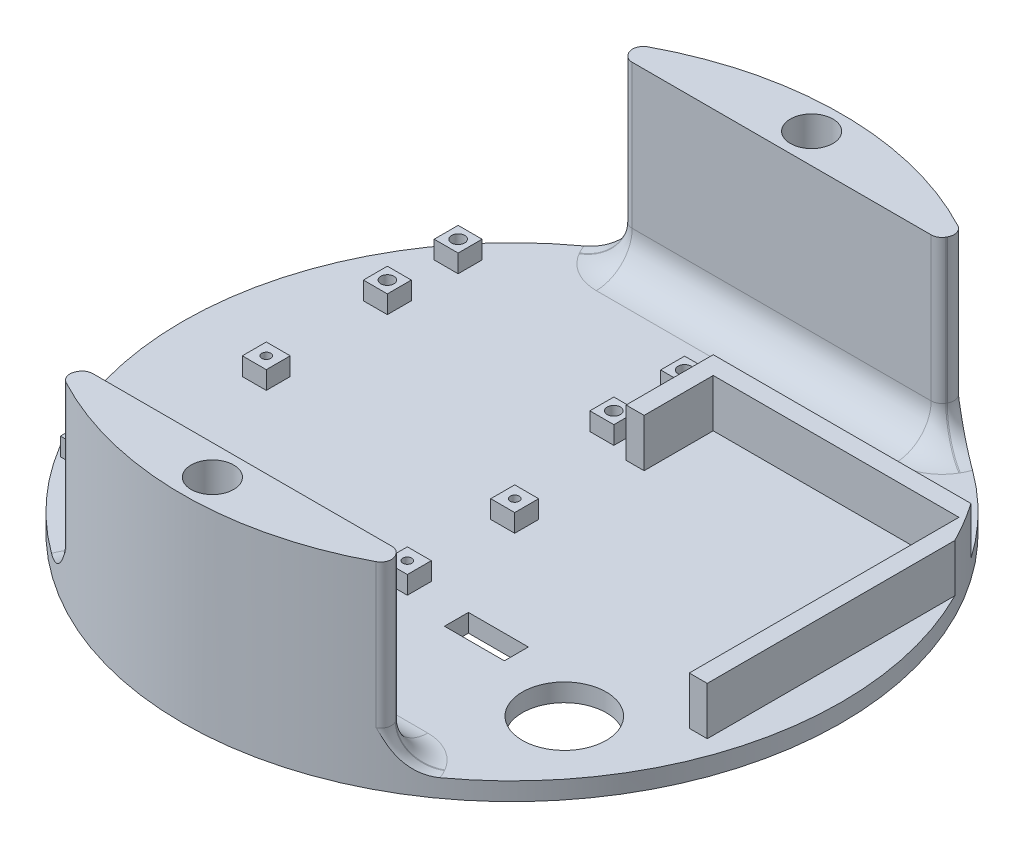
SolidWorks part; units mm, degrees
ref_plane "Front Plane" through (0, 0, 0) normal (0, 0, 1) x (1, 0, 0)
ref_plane "Top Plane" through (0, 0, 0) normal (0, 1, 0) x (1, 0, 0)
ref_plane "Right Plane" through (0, 0, 0) normal (1, 0, 0) x (0, 0, -1)
sketch "Sketch1" plane through (0, 0, 0) normal (0, 1, 0) x (1, 0, 0)
  circle A0 centre (0, 0) radius 69.85
  dimension "D1" = 139.7
extrude "Boss-Extrude1" add sketch "Sketch1" along normal blind 3.81
sketch "Sketch2" plane through (0, 3.81, 0) normal (0, 1, 0) x (1, 0, 0)
  line L0 (-32.9956, 57.15) -> (32.9956, 57.15)
  line L3 (-34.925, 60.4919) -> (-32.9956, 57.15)
  line L6 (0, 0) -> (-34.925, 60.4919) construction
  line L7 (0, 0) -> (34.925, 60.4919) construction
  line L8 (32.9956, 57.15) -> (34.925, 60.4919)
  line L9 (-34.925, -60.4919) -> (-32.9956, -57.15)
  line L10 (34.925, -60.4919) -> (32.9956, -57.15)
  line L11 (-32.9956, -57.15) -> (32.9956, -57.15)
  arc A0 (-34.925, 60.4919) -> (34.925, 60.4919) centre (0, 0) cw
  circle A1 centre (0, 0) radius 69.85 construction
  arc A3 (-34.925, -60.4919) -> (34.925, -60.4919) centre (0, 0) ccw
  point P6 (0, 69.85)
  point P7 (0, -69.85)
  point P12 (0, 0)
  dimension "D1" = 12.7
  dimension "D2" = 60
extrude "Boss-Extrude2" add sketch "Sketch2" along normal blind 38.1
fillet "Fillet1" radius 2.286 8 edges at (34.925, 22.86, 60.4919) (32.9956, 22.86, 57.15) (-32.9956, 22.86, 57.15) (-34.925, 22.86, 60.4919) (34.925, 22.86, -60.4919) (32.9956, 22.86, -57.15) (-32.9956, 22.86, -57.15) (-34.925, 22.86, -60.4919)
fillet "Fillet2" radius 7.62 14 edges at (-33.9807, 3.81, 60.2506) (-33.7091, 3.81, 58.3858) (-32.8187, 3.81, 57.4563) (0, 3.81, 57.15) (33.9807, 3.81, 60.2506) (33.7091, 3.81, 58.3858) (33.9807, 3.81, -60.2506) (33.7091, 3.81, -58.3858) (32.8187, 3.81, -57.4563) (0, 3.81, -57.15) (-32.8187, 3.81, -57.4563) (-33.7091, 3.81, -58.3858) (32.8187, 3.81, 57.4563) (-33.9807, 3.81, -60.2506)
sketch "Sketch3" plane through (0, 41.91, 0) normal (0, 1, 0) x (1, 0, 0)
  line L0 (0, 63.5) -> (0, -63.5) construction
  circle A0 centre (0, 63.5) radius 4.5085
  circle A1 centre (0, -63.5) radius 4.5085
  point P2 (0, 0)
  point P9 (0, 0)
  point P10 (0, 0)
  dimension "D1" = 127
  dimension "D2" = 9.017
extrude "Cut-Extrude1" cut sketch "Sketch3" against normal through all
sketch "Sketch4" plane through (0, 3.81, 0) normal (0, 1, 0) x (1, 0, 0)
  line L0 (-3.94, 25.52) -> (-3.94, 40.52) construction
  line L1 (-51.94, 25.52) -> (-51.94, 40.52) construction
  line L2 (-51.94, 25.52) -> (-3.94, 25.52) construction
  line L3 (-3.94, 40.52) -> (-51.94, 40.52) construction
  line L4 (-51.94, 25.52) -> (-3.94, 40.52) construction
  line L5 (-3.94, 25.52) -> (-51.94, 40.52) construction
  line L7 (4.1849, -37.6644) -> (4.1849, 19.8844) construction
  line L8 (4.1849, -37.6644) -> (-57.8651, -37.6644) construction
  line L9 (-57.8651, -37.6644) -> (-57.8651, 19.8844) construction
  line L10 (4.1849, 19.8844) -> (-57.8651, 19.8844) construction
  line L11 (4.1849, -37.6644) -> (-57.8651, 19.8844) construction
  line L12 (-57.8651, -37.6644) -> (4.1849, 19.8844) construction
  line L13 (6.4534, -20.9574) -> (58.5234, -20.9574) construction
  line L14 (6.4534, -20.9574) -> (6.4534, 36.1926) construction
  line L15 (6.4534, 36.1926) -> (58.5234, 36.1926) construction
  line L16 (58.5234, -20.9574) -> (58.5234, 36.1926) construction
  line L17 (6.4534, -20.9574) -> (58.5234, 36.1926) construction
  line L18 (6.4534, 36.1926) -> (58.5234, -20.9574) construction
  circle A0 centre (-51.94, 25.52) radius 1.397
  circle A1 centre (-51.94, 40.52) radius 1.397
  circle A2 centre (-3.94, 25.52) radius 1.397
  circle A3 centre (-3.94, 40.52) radius 1.397
  circle A4 centre (-55.4151, -35.2144) radius 0.95
  circle A5 centre (-50.8651, -1.2144) radius 0.95
  circle A6 centre (1.6849, -1.1144) radius 0.95
  circle A7 centre (1.6849, -23.8652) radius 0.95
  circle A8 centre (43.0469, -31.9652) radius 8.89
  point P0 (-26.8401, -8.89)
  point P2 (32.4884, 7.6176)
  point P10 (-27.94, 33.02)
  point P27 (0, 0)
  point P28 (0, 0)
  point P32 (-2.6478, 1.6705)
  point P33 (0, 0)
  dimension "D1" = 2.794
  dimension "D2" = 15
  dimension "D3" = 48
  dimension "D4" = 62.05
  dimension "D8" = 2.45
  dimension "D10" = 1.9
  dimension "D11" = 34
  dimension "D13" = 52.55
  dimension "D15" = 22.7508
  dimension "D17" = 38.862
  dimension "D19" = 17.78
  dimension "D5" = 57.5488
  dimension "D6" = 52.07
  dimension "D7" = 57.15
  dimension "D9" = 2.45
  dimension "D12" = 4.55
  dimension "D14" = 0.1
  dimension "D16" = 52.55
  dimension "D18" = 8.1
  dimension "D20" = 26.8401
  dimension "D21" = 8.89
  dimension "D22" = 27.94
  dimension "D23" = 33.02
  dimension "D24" = 32.4884
  dimension "D25" = 7.6176
extrude "Cut-Extrude2" cut sketch "Sketch4" against normal through all
sketch "Sketch5" plane through (0, 3.81, 0) normal (0, 1, 0) x (1, 0, 0)
  line L1 (-53.4051, -3.7544) -> (-48.3251, -3.7544)
  line L2 (-53.4051, -3.7544) -> (-53.4051, 1.3256)
  line L3 (-53.4051, 1.3256) -> (-48.3251, 1.3256)
  line L4 (-48.3251, -3.7544) -> (-48.3251, 1.3256)
  line L5 (-53.4051, -3.7544) -> (-48.3251, 1.3256) construction
  line L6 (-53.4051, 1.3256) -> (-48.3251, -3.7544) construction
  line L7 (-57.9551, -37.7544) -> (-52.8751, -37.7544)
  line L8 (-57.9551, -37.7544) -> (-57.9551, -32.6744)
  line L9 (-57.9551, -32.6744) -> (-52.8751, -32.6744)
  line L10 (-52.8751, -37.7544) -> (-52.8751, -32.6744)
  line L11 (-57.9551, -37.7544) -> (-52.8751, -32.6744) construction
  line L12 (-57.9551, -32.6744) -> (-52.8751, -37.7544) construction
  line L13 (-0.8551, -26.4052) -> (4.2249, -26.4052)
  line L14 (-0.8551, -26.4052) -> (-0.8551, -21.3252)
  line L15 (-0.8551, -21.3252) -> (4.2249, -21.3252)
  line L16 (4.2249, -26.4052) -> (4.2249, -21.3252)
  line L17 (-0.8551, -26.4052) -> (4.2249, -21.3252) construction
  line L18 (-0.8551, -21.3252) -> (4.2249, -26.4052) construction
  line L19 (-0.8551, 1.4256) -> (4.2249, 1.4256)
  line L20 (-0.8551, 1.4256) -> (-0.8551, -3.6544)
  line L21 (-0.8551, -3.6544) -> (4.2249, -3.6544)
  line L22 (4.2249, 1.4256) -> (4.2249, -3.6544)
  line L23 (-0.8551, 1.4256) -> (4.2249, -3.6544) construction
  line L24 (-0.8551, -3.6544) -> (4.2249, 1.4256) construction
  line L25 (-6.48, 28.06) -> (-1.4, 28.06)
  line L26 (-6.48, 28.06) -> (-6.48, 22.98)
  line L27 (-6.48, 22.98) -> (-1.4, 22.98)
  line L28 (-1.4, 28.06) -> (-1.4, 22.98)
  line L29 (-6.48, 28.06) -> (-1.4, 22.98) construction
  line L30 (-6.48, 22.98) -> (-1.4, 28.06) construction
  line L31 (-6.48, 43.06) -> (-1.4, 43.06)
  line L32 (-6.48, 43.06) -> (-6.48, 37.98)
  line L33 (-6.48, 37.98) -> (-1.4, 37.98)
  line L34 (-1.4, 43.06) -> (-1.4, 37.98)
  line L35 (-6.48, 43.06) -> (-1.4, 37.98) construction
  line L36 (-6.48, 37.98) -> (-1.4, 43.06) construction
  line L37 (-54.48, 43.06) -> (-49.4, 43.06)
  line L38 (-54.48, 43.06) -> (-54.48, 37.98)
  line L39 (-54.48, 37.98) -> (-49.4, 37.98)
  line L40 (-49.4, 43.06) -> (-49.4, 37.98)
  line L41 (-54.48, 43.06) -> (-49.4, 37.98) construction
  line L42 (-54.48, 37.98) -> (-49.4, 43.06) construction
  line L43 (-54.48, 28.06) -> (-49.4, 28.06)
  line L44 (-54.48, 28.06) -> (-54.48, 22.98)
  line L45 (-54.48, 22.98) -> (-49.4, 22.98)
  line L46 (-49.4, 28.06) -> (-49.4, 22.98)
  line L47 (-54.48, 28.06) -> (-49.4, 22.98) construction
  line L48 (-54.48, 22.98) -> (-49.4, 28.06) construction
  circle A0 centre (-55.4151, -35.2144) radius 0.95
  circle A1 centre (1.6849, -23.8652) radius 0.95
  circle A2 centre (1.6849, -1.1144) radius 0.95
  circle A3 centre (-50.8651, -1.2144) radius 0.95
  circle A4 centre (-51.94, 25.52) radius 1.397
  circle A5 centre (-3.94, 25.52) radius 1.397
  circle A6 centre (-3.94, 40.52) radius 1.397
  circle A7 centre (-51.94, 40.52) radius 1.397
  circle A8 centre (-55.4151, -35.2144) radius 0.95 construction
  circle A9 centre (1.6849, -23.8652) radius 0.95 construction
  circle A10 centre (1.6849, -1.1144) radius 0.95 construction
  circle A11 centre (-50.8651, -1.2144) radius 0.95 construction
  circle A12 centre (-51.94, 25.52) radius 1.397 construction
  circle A13 centre (-51.94, 40.52) radius 1.397 construction
  circle A14 centre (-3.94, 25.52) radius 1.397 construction
  circle A15 centre (-3.94, 40.52) radius 1.397 construction
  point P0 (-50.8651, -1.2144)
  point P5 (-55.4151, -35.2144)
  point P11 (1.6849, -23.8652)
  point P17 (1.6849, -1.1144)
  point P23 (-3.94, 25.52)
  point P29 (-3.94, 40.52)
  point P35 (-51.94, 40.52)
  point P41 (-51.94, 25.52)
  dimension "D1" = 5.08
extrude "Boss-Extrude3" add sketch "Sketch5" along normal blind 3.81
sketch "Sketch6" plane through (0, 3.81, 0) normal (0, 1, 0) x (1, 0, 0)
  line L0 (2.6434, 21.5377) -> (2.6434, 40.0026)
  line L2 (58.5234, 36.1926) -> (58.5234, -20.9574)
  line L3 (58.5234, -20.9574) -> (62.3334, -20.9574)
  line L4 (62.3334, 31.521) -> (62.3334, -20.9574)
  line L5 (2.6434, 40.0026) -> (57.2609, 40.0026)
  line L6 (6.4534, 21.5377) -> (2.6434, 21.5377)
  line L7 (6.4534, 21.5377) -> (6.4534, 36.1926)
  line L15 (6.4534, 36.1926) -> (58.5234, 36.1926) construction
  line L16 (6.4534, 36.1926) -> (6.4534, -20.9574) construction
  line L17 (6.4534, -20.9574) -> (58.5234, -20.9574) construction
  line L18 (58.5234, 36.1926) -> (58.5234, -20.9574) construction
  line L21 (6.4534, 36.1926) -> (58.5234, 36.1926)
  arc A0 (62.3334, 31.521) -> (57.2609, 40.0026) centre (0, 0) ccw
  circle A3 centre (0, 0) radius 69.85 construction
  point P10 (0, 0)
  point P15 (0, 0)
  point P16 (58.5234, 38.2143)
  point P17 (57.2609, 40.0026)
  point P19 (0, 0)
  dimension "D2" = 3.81
  dimension "D1" = 3.81
  dimension "D3" = 3.81
  dimension "D4" = 18.465
extrude "Boss-Extrude4" add sketch "Sketch6" along normal blind 10.16
sketch "Sketch7" plane through (0, 3.81, 0) normal (0, 1, 0) x (1, 0, 0)
  line L1 (13.8369, -23.0752) -> (26.5369, -23.0752)
  line L2 (13.8369, -23.0752) -> (13.8369, -28.1552)
  line L3 (13.8369, -28.1552) -> (26.5369, -28.1552)
  line L4 (26.5369, -23.0752) -> (26.5369, -28.1552)
  line L5 (57.2609, 40.0026) -> (2.6434, 40.0026) construction
  line L6 (13.8369, 40.0026) -> (49.3969, 40.0026)
  line L7 (13.8369, 40.0026) -> (13.8369, 45.0826)
  line L8 (13.8369, 45.0826) -> (49.3969, 45.0826)
  line L9 (49.3969, 40.0026) -> (49.3969, 45.0826)
  circle A0 centre (43.0469, -31.9652) radius 8.89 construction
  point P13 (0, 0)
  dimension "D1" = 5.08
  dimension "D2" = 16.51
  dimension "D3" = 12.7
  dimension "D4" = 5.08
  dimension "D5" = 6.35
extrude "Cut-Extrude3" cut sketch "Sketch7" against normal through all
